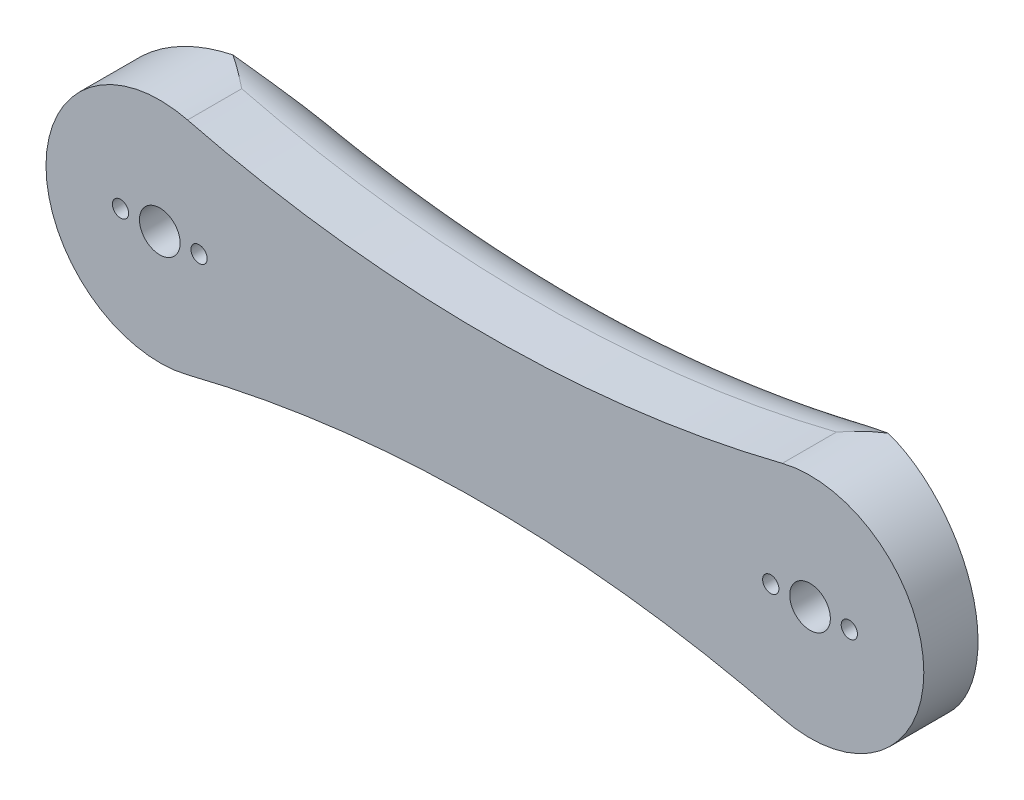
SolidWorks part; units mm, degrees
ref_plane "Alzado" through (0, 0, 0) normal (0, 0, 1) x (1, 0, 0)
ref_plane "Planta" through (0, 0, 0) normal (0, 1, 0) x (1, 0, 0)
ref_plane "Vista lateral" through (0, 0, 0) normal (1, 0, 0) x (0, 0, -1)
sketch "Croquis1" plane through (0, 0, 0) normal (0, 0, 1) x (1, 0, 0)
  line L0 (-60, 0) -> (60, 0) construction
  circle A0 centre (-60, 0) radius 21
  circle A1 centre (60, 0) radius 21
  arc A2 (-54.878, 20.3658) -> (54.878, 20.3658) centre (0, 238.5707) ccw
  arc A3 (54.878, -20.3658) -> (-54.878, -20.3658) centre (0, -238.5707) ccw
  point P4 (0, 0)
  dimension "D1" = 120
  dimension "D2" = 42
  dimension "D3" = 42
  dimension "D4" = 450
  dimension "D5" = 450
extrude "Saliente-Extruir1" add sketch "Croquis1" against normal blind 20 contours L0 A0 A3 A1 | A0 L0 A1 A2 | A1 | A0 region at (0, 7.9583, 0) region at (-43.907, -12.5468, 0) region at (0, -7.9583, 0) region at (43.907, 12.5468, 0)
sketch "Croquis2" plane through (0, 0, 0) normal (0, 1, 0) x (1, 0, 0)
  line L0 (-81, 10) -> (-81, 20)
  line L1 (-81, 20) -> (-81, 0) construction
  line L2 (-81, 20) -> (-39, 20)
  line L3 (54.878, 20) -> (-54.878, 20) construction
  line L4 (0, -11) -> (0, 11) construction
  line L5 (81, 10) -> (81, 20)
  line L6 (81, 20) -> (39, 20)
  arc A0 (-81, 10) -> (-39, 20) centre (-119.5622, 265.1614) ccw
  arc A1 (81, 10) -> (39, 20) centre (119.5622, 265.1614) cw
  dimension "D2" = 258.0589
  dimension "D1" = 42
extrude "Cortar-Extruir1" cut sketch "Croquis2" against normal through all both and the other way through all
sketch "Croquis4" plane through (0, 0, -20) normal (0, 0, -1) x (-1, 0, 0)
  circle A0 centre (60, 0) radius 18
  circle A1 centre (-60, 0) radius 18
  dimension "D1" = 36
  dimension "D2" = 36
extrude "Cortar-Extruir2" cut sketch "Croquis4" against normal blind 14
sketch "Croquis5" plane through (0, 0, -6) normal (0, 0, -1) x (-1, 0, 0)
  line L0 (60, 0) -> (60, 7.6258) construction
  line L1 (60, 0) -> (67.25, 0) construction
  line L2 (0, 11) -> (0, -11) construction
  circle A0 centre (60, 0) radius 3.75
  circle A1 centre (67.25, 0) radius 1.5
  circle A2 centre (52.75, 0) radius 1.5
  circle A3 centre (-67.25, 0) radius 1.5
  circle A4 centre (-60, 0) radius 3.75
  circle A5 centre (-52.75, 0) radius 1.5
  dimension "D1" = 7.5
  dimension "D2" = 3
  dimension "D3" = 7.25
extrude "Cortar-Extruir3" cut sketch "Croquis5" against normal through all
fillet "Redondeo1" radius 10 2 edges at (0, -13.5707, -20) (0, 13.5707, -20)
sketch "Croquis6" plane through (0, 0, 0) normal (1, 0, 0) x (0, 0, -1)
  line L0 (6, -5.5) -> (6, 5.5) construction
  line L1 (6, -18) -> (6, 18) construction
  line L2 (6, 0) -> (13, 0) construction
  line L3 (6, 5.5) -> (6, -5.5)
  arc A0 (6, 5.5) -> (6, -5.5) centre (7.3393, 0) cw
  dimension "D1" = 5.5
  dimension "D2" = 7
extrude "Cortar-Extruir4" cut sketch "Croquis6" against normal mid plane 94
